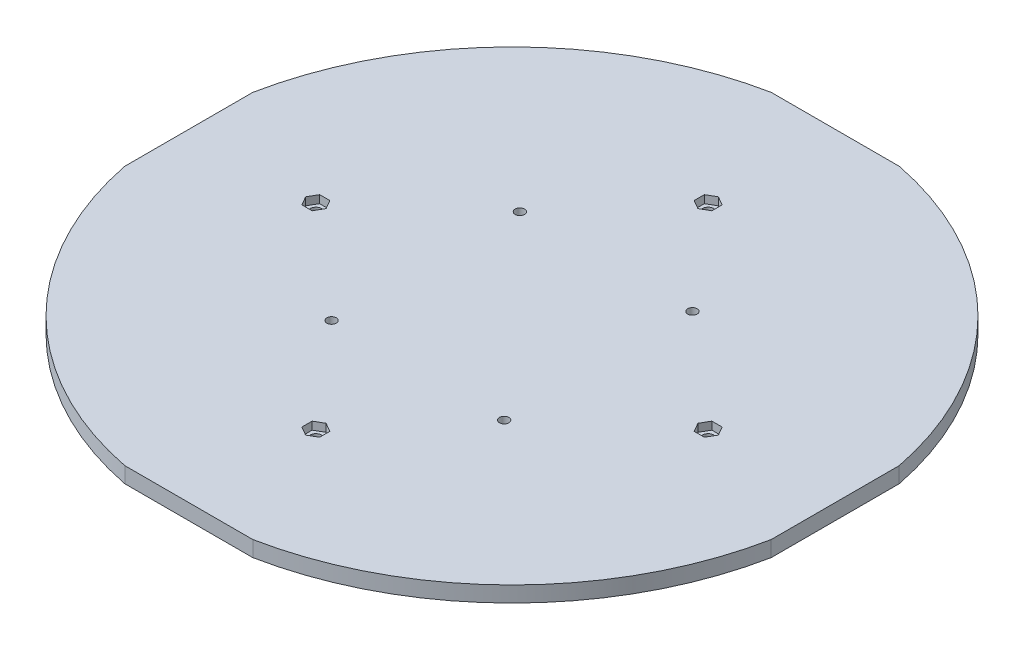
SolidWorks part; units mm, degrees
ref_plane "Front Plane" through (0, 0, 0) normal (0, 0, 1) x (1, 0, 0)
ref_plane "Top Plane" through (0, 0, 0) normal (0, 1, 0) x (1, 0, 0)
ref_plane "Right Plane" through (0, 0, 0) normal (1, 0, 0) x (0, 0, -1)
sketch "Sketch1" plane through (0, 0, 0) normal (0, 1, 0) x (1, 0, 0)
  line L0 (0, -55) -> (0, 55) construction
  line L1 (-55, 0) -> (55, 0) construction
  circle A0 centre (0, 0) radius 105
  circle A1 centre (-27.5, 30) radius 1.5
  circle A2 centre (27.5, 30) radius 1.5
  circle A3 centre (27.5, -30) radius 1.5
  circle A4 centre (-27.5, -30) radius 1.5
  dimension "D1" = 210
  dimension "D2" = 3
  dimension "D3" = 27.5
  dimension "D4" = 30
extrude "Boss-Extrude1" add sketch "Sketch1" along normal blind 5
sketch "Sketch2" plane through (0, 5, 0) normal (0, 1, 0) x (1, 0, 0)
  line L0 (-62.5, 0) -> (62.5, 0) construction
  line L1 (0, 62.5) -> (0, -62.5) construction
  line L2 (-2.825, 60.869) -> (0, 59.238)
  line L3 (-60.869, -2.825) -> (-59.238, 0)
  line L4 (-59.238, 0) -> (-60.869, 2.825)
  line L5 (-60.869, 2.825) -> (-64.131, 2.825)
  line L6 (-64.131, 2.825) -> (-65.762, 0)
  line L7 (-65.762, 0) -> (-64.131, -2.825)
  line L8 (-64.131, -2.825) -> (-60.869, -2.825)
  line L9 (0, 59.238) -> (2.825, 60.869)
  line L10 (2.825, 60.869) -> (2.825, 64.131)
  line L11 (2.825, 64.131) -> (0, 65.762)
  line L12 (0, 65.762) -> (-2.825, 64.131)
  line L13 (-2.825, 64.131) -> (-2.825, 60.869)
  line L14 (60.869, 2.825) -> (59.238, 0)
  line L15 (59.238, 0) -> (60.869, -2.825)
  line L16 (60.869, -2.825) -> (64.131, -2.825)
  line L17 (64.131, -2.825) -> (65.762, 0)
  line L18 (65.762, 0) -> (64.131, 2.825)
  line L19 (64.131, 2.825) -> (60.869, 2.825)
  line L20 (2.825, -60.869) -> (0, -59.238)
  line L21 (0, -59.238) -> (-2.825, -60.869)
  line L22 (-2.825, -60.869) -> (-2.825, -64.131)
  line L23 (-2.825, -64.131) -> (0, -65.762)
  line L24 (0, -65.762) -> (2.825, -64.131)
  line L25 (2.825, -64.131) -> (2.825, -60.869)
  circle A0 centre (-62.5, 0) radius 2.825 construction
  circle A1 centre (0, 62.5) radius 2.825 construction
  circle A2 centre (62.5, 0) radius 2.825 construction
  circle A3 centre (0, -62.5) radius 2.825 construction
  circle A4 centre (-62.5, 0) radius 1.8
  circle A5 centre (0, 62.5) radius 1.8
  circle A6 centre (62.5, 0) radius 1.8
  circle A7 centre (0, -62.5) radius 1.8
  point P5 (0, 0)
  point P9 (0, 0)
  point P43 (0, 0)
  point P51 (0, 0)
  dimension "D4" = 3.6
  dimension "D5" = 4
  dimension "D1" = 125
  dimension "D2" = 5.65
  dimension "D3" = 4
extrude "Cut-Extrude1" cut sketch "Sketch2" against normal blind 2.5 contours A7 | L24 L25 L20 L21 L22 L23 A7 | A4 | L7 L8 L3 L4 L5 L6 A4 | A5 | L12 L13 L2 L9 L10 L11 A5 | A6 | L18 L19 L14 L15 L16 L17 A6 region at (-2.7387, 5, -62.5) region at (-62.5, 5, 2.7387) region at (62.5, 5, -2.7387) region at (2.7387, 5, 62.5) region at (-62.5, 5, 0) region at (0, 5, -62.5) region at (62.5, 5, 0) region at (0, 5, 62.5)
extrude "Cut-Extrude3" cut sketch "Sketch2<3>" against normal through all contours A5 | A6 | A7 | A4 region at (0, 5, -62.5) region at (62.5, 5, 0) region at (0, 5, 62.5)
sketch "Sketch2<3>" plane through (0, 5, 0) normal (0, 1, 0) x (1, 0, 0) same geometry as "Sketch2"
sketch "Sketch4" plane through (0, 5, 0) normal (0, 1, 0) x (1, 0, 0)
  line L0 (-20.3961, 103) -> (20.3961, 103)
  line L1 (103, 20.3961) -> (103, -20.3961)
  line L2 (20.3961, -103) -> (-20.3961, -103)
  line L3 (-103, -20.3961) -> (-103, 20.3961)
  circle A0 centre (0, 0) radius 105 construction
  circle A2 centre (0, 0) radius 105
  point P13 (0, 0)
  circle M28 centre (0, 0) radius 105
  dimension "D1" = 103
  dimension "D2" = 4
extrude "Cut-Extrude4" cut sketch "Sketch4" against normal through all contours L3 M28 | L2 M28 | L1 M28 | L0 M28 region at (0, 5, -103.8007) region at (-103.8007, 5, 0) region at (103.8007, 5, 0) region at (0, 5, 103.8007)
